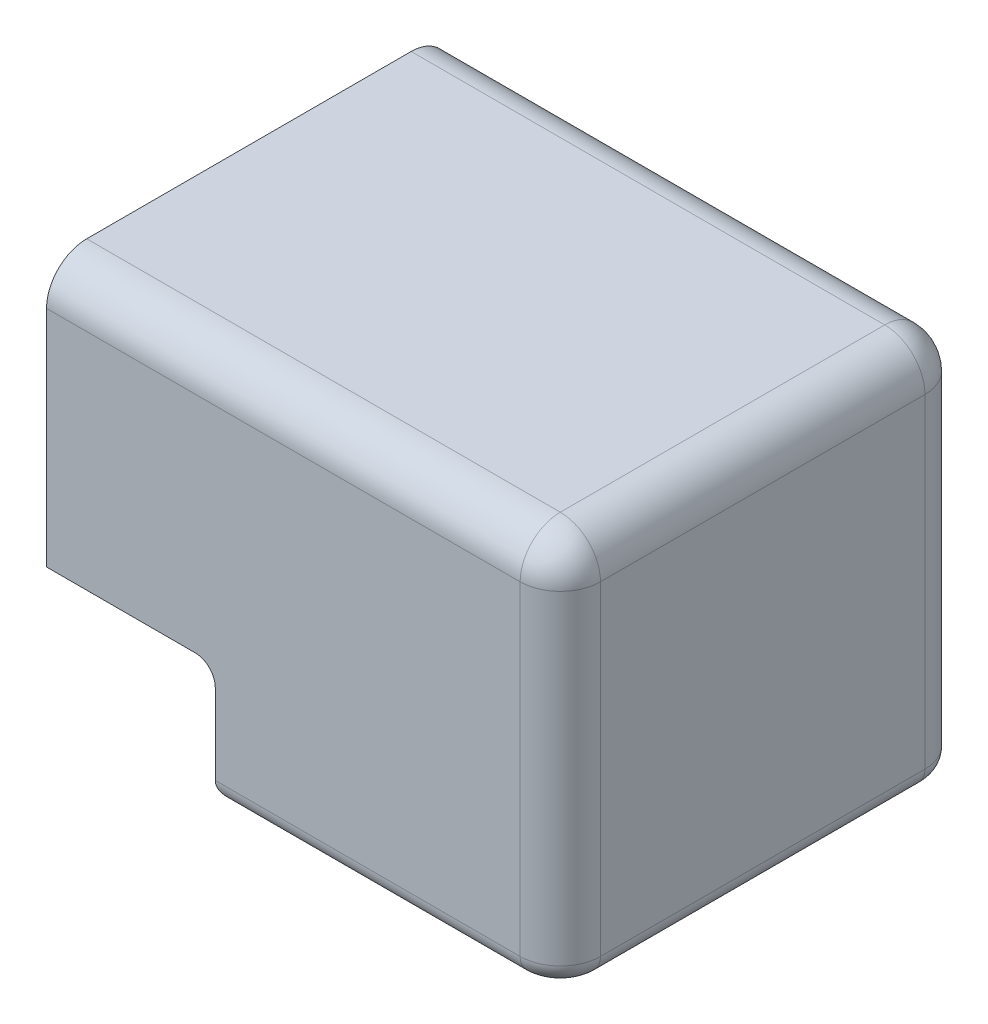
SolidWorks part; units mm, degrees
material "ABS"
ref_plane "X-Y Datum" through (0, 0, 0) normal (0, 0, 1) x (1, 0, 0)
ref_plane "X-Z Datum" through (0, 0, 0) normal (0, 1, 0) x (1, 0, 0)
ref_plane "Y-Z Datum" through (0, 0, 0) normal (1, 0, 0) x (0, 0, -1)
sketch "Sketch1" plane through (0, 0, 0) normal (1, 0, 0) x (0, 0, -1)
  line L0 (100.5047, -7.0485) -> (113.2047, 7.0485)
  line L1 (113.2047, -7.0485) -> (100.5047, 7.0485)
  line L3 (79.8672, -15.875) -> (133.8422, -15.875)
  line L4 (79.8672, -15.875) -> (79.8672, 15.875)
  line L5 (79.8672, 15.875) -> (133.8422, 15.875)
  line L6 (133.8422, -15.875) -> (133.8422, 15.875)
  line L7 (79.8672, -15.875) -> (133.8422, 15.875) construction
  line L8 (79.8672, 15.875) -> (133.8422, -15.875) construction
  point P4 (106.8547, 0)
  dimension "D1" = 31.75
  dimension "D2" = 53.975
extrude "Boss-Extrude1" add sketch "Sketch1" along normal blind 76.2 contours L3 L6 L5 region at (0, 0, -80.4934)
shell "Shell1" thickness 5 removed face at (0, 0, -106.8547) outward yes
sketch "Sketch2" plane through (0, -20.875, 0) normal (0, -1, 0) x (-1, 0, 0)
  line L0 (-76.2, 133.8422) -> (0, 133.8422) construction
  line L1 (-76.2, 79.8672) -> (-76.2, 133.8422) construction
  line L2 (-76.2, 79.8672) -> (0, 79.8672) construction
  line L3 (-76.2, 133.8422) -> (0, 133.8422)
  line L4 (-76.2, 79.8672) -> (-76.2, 133.8422)
  line L5 (-76.2, 79.8672) -> (0, 79.8672)
  line L6 (-31.75, 79.8672) -> (-31.75, 133.8422)
  dimension "D1" = 44.45
extrude "Cut-Extrude1" cut sketch "Sketch2" against normal blind 5 contours L5 L6 L3 L4 region at (53.975, -20.875, -106.8547)
fillet "Fillet1" radius 31.75 1 edges at (76.2, 15.875, -106.8547)
fillet "Fillet2" radius 6.35 1 edges at (31.75, -15.875, -106.8547)
fillet "Fillet3" radius 6.35 5 edges at (40.6, 20.875, -138.8422) (81.2, 20.875, -106.8547) (40.6, 20.875, -74.8672) (81.2, 0, -138.8422) (81.2, 0, -74.8672)
sketch "Sketch3" plane through (0, -20.875, 0) normal (0, -1, 0) x (1, 0, 0)
  line L0 (31.75, -79.8672) -> (31.75, -133.8422) construction
  line L1 (76.2, -79.8672) -> (31.75, -79.8672) construction
  line L2 (76.2, -79.8672) -> (76.2, -133.8422) construction
  line L3 (76.2, -133.8422) -> (31.75, -133.8422) construction
  line L4 (0, -138.8422) -> (74.85, -138.8422)
  line L5 (81.2, -132.4922) -> (81.2, -81.2172)
  line L6 (74.85, -74.8672) -> (0, -74.8672)
  line L7 (0, -74.8672) -> (0, -138.8422)
  line L8 (0, -138.8422) -> (74.85, -138.8422)
  line L9 (81.2, -132.4922) -> (81.2, -81.2172)
  line L10 (74.85, -74.8672) -> (0, -74.8672)
  line L11 (0, -74.8672) -> (0, -138.8422)
  line L12 (76.2, -79.8672) -> (31.75, -79.8672)
  line L13 (31.75, -79.8672) -> (31.75, -133.8422)
  line L14 (76.2, -133.8422) -> (31.75, -133.8422)
  line L15 (76.2, -79.8672) -> (76.2, -133.8422)
  line L16 (26.67, -138.8422) -> (26.67, -74.8672)
  arc A2 (74.85, -138.8422) -> (81.2, -132.4922) centre (74.85, -132.4922) ccw
  arc A3 (81.2, -81.2172) -> (74.85, -74.8672) centre (74.85, -81.2172) ccw
  arc A4 (74.85, -138.8422) -> (81.2, -132.4922) centre (74.85, -132.4922) ccw
  arc A5 (81.2, -81.2172) -> (74.85, -74.8672) centre (74.85, -81.2172) ccw
  line M10 (31.75, -133.8422) -> (31.75, -79.8672)
  line M11 (31.75, -79.8672) -> (76.2, -79.8672)
  line M12 (76.2, -79.8672) -> (76.2, -133.8422)
  line M13 (76.2, -133.8422) -> (31.75, -133.8422)
  arc M15 (74.85, -138.8422) -> (81.2, -132.4922) centre (74.85, -132.4922) ccw
  line M16 (81.2, -132.4922) -> (81.2, -81.2172)
  arc M17 (81.2, -81.2172) -> (74.85, -74.8672) centre (74.85, -81.2172) ccw
  line M18 (74.85, -74.8672) -> (0, -74.8672)
  dimension "D2" = 5
  dimension "D3" = 5.08
  dimension "D1" = 0
extrude "Boss-Extrude2" add sketch "Sketch3" along normal blind 19.05 contours L16 L8 M15 M16 M17 M18 M13 M10 M11 M12 region at (27.5106, -20.875, -106.8547)
fillet "Fillet5" radius 3.175 1 edges at (26.67, -20.875, -106.8547)
fillet "Fillet6" radius 3.175 6 edges at (50.76, -39.925, -138.8422) (79.3401, -39.925, -136.9823) (81.2, -39.925, -106.8547) (79.3401, -39.925, -76.727) (26.67, -39.925, -106.8547) (50.76, -39.925, -74.8672)
